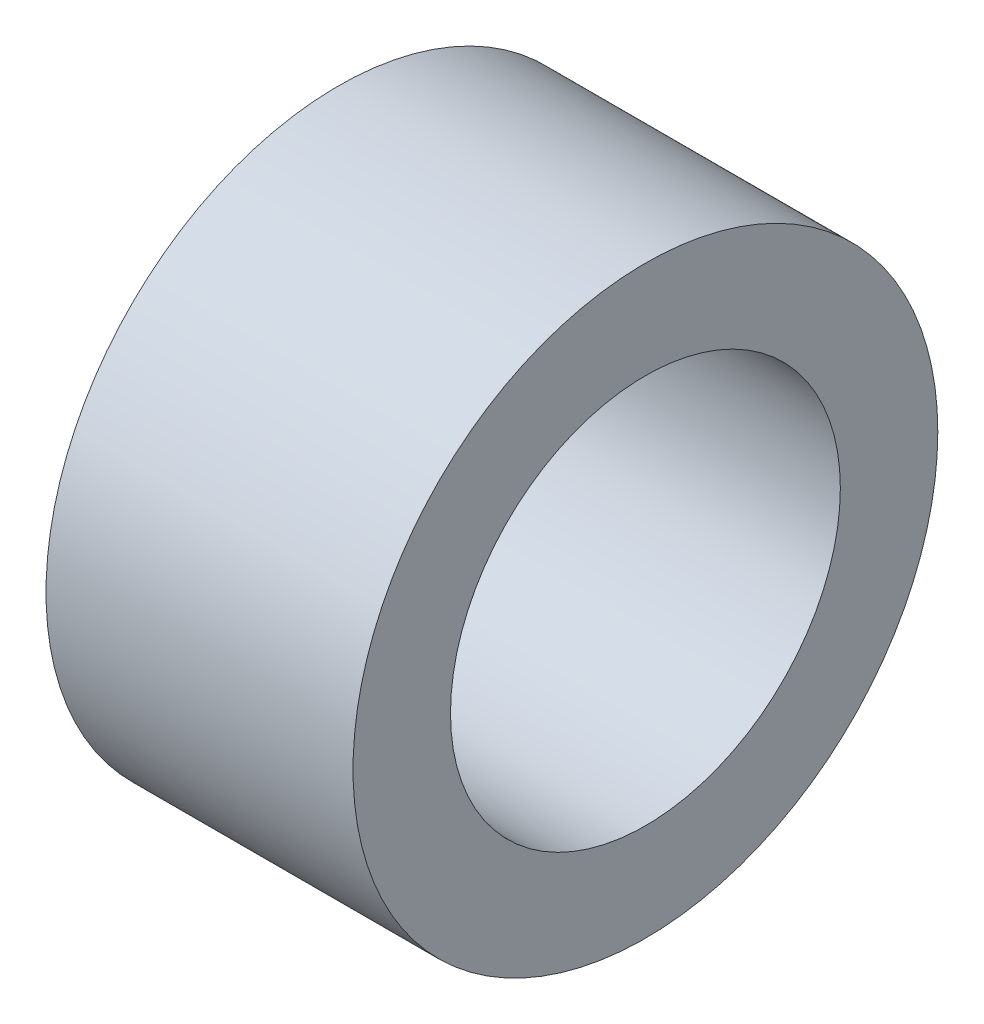
SolidWorks part; units mm, degrees
ref_plane "Front Plane" through (0, 0, 0) normal (0, 0, 1) x (1, 0, 0)
ref_plane "Top Plane" through (0, 0, 0) normal (0, 1, 0) x (1, 0, 0)
ref_plane "Right Plane" through (0, 0, 0) normal (1, 0, 0) x (0, 0, -1)
sketch "Sketch1" plane through (0, 0, 0) normal (1, 0, 0) x (0, 0, -1)
  circle A0 centre (-19.0771, 3.5611) radius 12
  circle A1 centre (-19.0771, 3.5611) radius 8
extrude "Boss-Extrude1" add sketch "Sketch1" along normal blind 6.3 and the other way blind 6.3 contours A1 | A0
